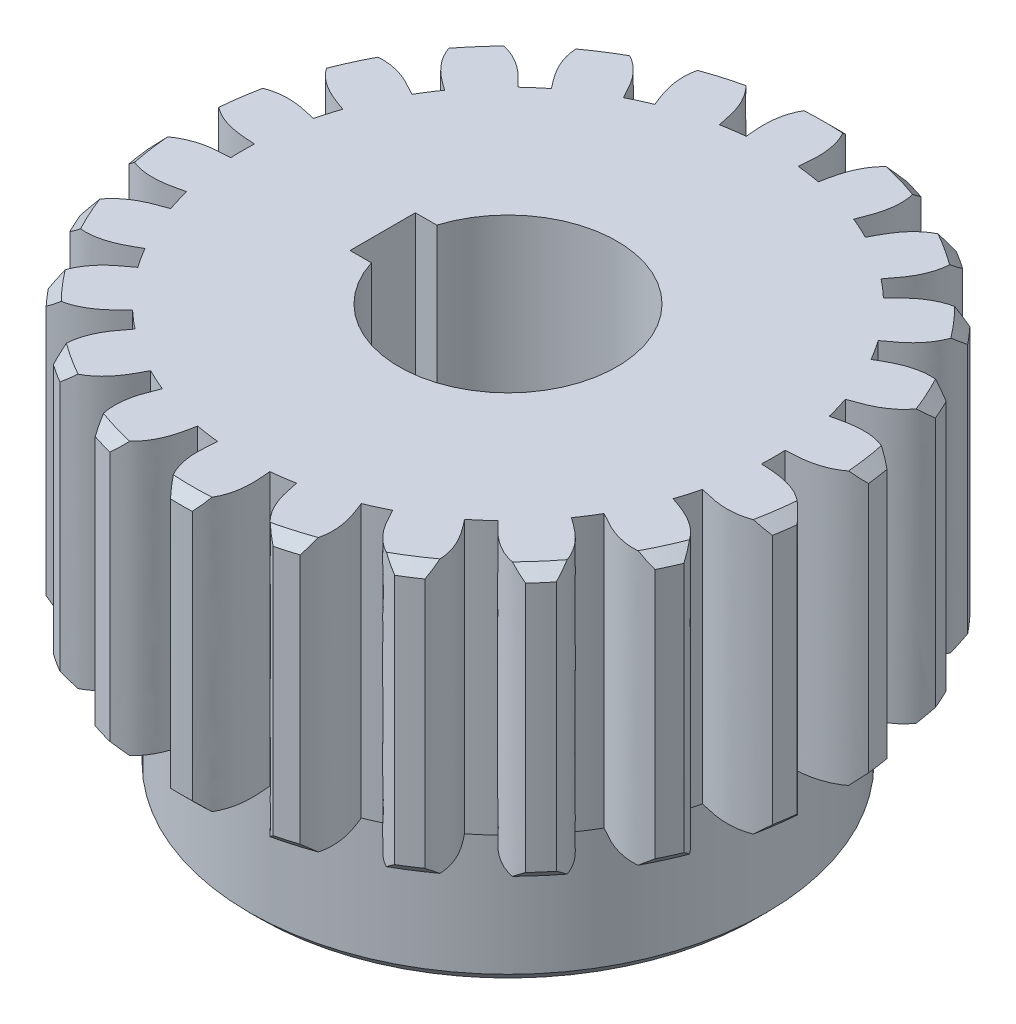
SolidWorks part; units mm, degrees
ref_plane "前基準面" through (0, 0, 0) normal (0, 0, 1) x (1, 0, 0)
ref_plane "上基準面" through (0, 0, 0) normal (0, 1, 0) x (1, 0, 0)
ref_plane "右基準面" through (0, 0, 0) normal (1, 0, 0) x (0, 0, -1)
sketch "草圖1" plane through (0, 0, 0) normal (0, 0, 1) x (1, 0, 0)
  line L0 (0, -10.9151) -> (0, 15.1539) construction
  line L1 (20, 50) -> (60, 50)
  line L2 (60, 50) -> (60, 0)
  line L3 (60, 0) -> (47.5, 0)
  line L4 (47.5, 0) -> (47.5, -25)
  line L5 (47.5, -25) -> (20, -25)
  line L6 (20, -25) -> (20, 50)
  dimension "D1" = 75
  dimension "D2" = 50
  dimension "D3" = 40
  dimension "D4" = 120
  dimension "D5" = 95
revolve "旋轉1" add sketch "草圖1" angle 360 about L0
sketch "草圖2" plane through (0, 50, 0) normal (0, 1, 0) x (1, 0, 0)
  line L0 (0, 0) -> (-25.7975, 0) construction
  line L1 (-23, 6) -> (-11, 6)
  line L2 (-23, 6) -> (-23, -6)
  line L3 (-23, -6) -> (-11, -6)
  line L4 (-11, 6) -> (-11, -6)
  circle A0 centre (0, 0) radius 20 construction
  dimension "D1" = 43
  dimension "D2" = 12
extrude "除料-伸長1" cut sketch "草圖2" against normal up to next
chamfer "導角1" distance 2 angle 45 3 edges at (0, 0, -60) (0, 50, -60) (0, -25, -47.5)
sketch "草圖7" plane through (0, 0, 0) normal (0, -1, 0) x (1, 0, 0)
  line L0 (0, 0) -> (-66.5332, 0) construction
  circle A0 centre (0, 0) radius 55 construction
  arc A1 (-48.7016, 2.1717) -> (-48.7016, -2.1717) centre (0, 0) ccw
  circle A2 centre (0, 0) radius 60 construction
  arc A3 (-59.641, 6.5536) -> (-59.641, -6.5536) centre (0, 0) ccw
  circle A4 centre (0, 0) radius 58 construction
  circle A5 centre (0, 0) radius 60 construction
  spline S0 degree 3 poles (-59.641, 6.5536) (-59.0593, 5.9065) (-57.2741, 3.9209) (-53.2816, 2.3848) (-50.0991, 2.2367) (-48.7016, 2.1717) knots 0 0 0 0 0.213285 0.654527 1 1 1 1
  spline S1 degree 3 poles (-59.641, -6.5536) (-59.0593, -5.9065) (-57.2741, -3.9209) (-53.2816, -2.3848) (-50.0991, -2.2367) (-48.7016, -2.1717) knots 0 0 0 0 0.213285 0.654527 1 1 1 1
  dimension "D1" = 110
  dimension "D2" = 48.75
extrude "除料-伸長2" cut sketch "草圖7" against normal up to next
pattern_circular "環狀複製排列1" count 22 every 16.364 about axis through (0, 50.001, 0) along (0, -1, 0) of "除料-伸長2"
ref_plane "平面1" through (-60, 0, 0) normal (1, 0, 0) x (0, 0, -1)
hole_wizard "M8 螺紋孔1" positions "草圖4" profile "草圖3" tap size "M8" standard "GB" end condition up to next
sketch "草圖4" plane through (-60, 10, 0) normal (1, 0, 0) x (0, 0, -1)
  line L0 (0, -20.9151) -> (0, 5.1539) construction
  line L1 (-47.5, -35) -> (47.5, -35) construction
  point P0 (0, -25)
  dimension "D1" = 10
cosmetic thread "鑽孔螺紋1" parameters "D2"=8
sketch "草圖3" plane through (-60, -15, 0) normal (0, 1, 0) x (0, 0, 1)
  line L0 (0, 0) -> (0, 37)
  line L1 (0, 37) -> (3.4, 37)
  line L2 (3.4, 37) -> (3.4, 0)
  line L5 (3.4, 0) -> (0, 0)
  line L11 (0, -6.35) -> (0, 107.95) construction
  dimension "貫穿螺孔鑽直徑" = 6.8
  dimension "貫穿螺孔鑽深度" = 37
ref_plane "平面2" through (0, 0, -60) normal (0, 0, 1) x (1, 0, 0)
hole_wizard "M8 螺紋孔2" positions "草圖6" profile "草圖5" tap size "M8" standard "GB" end condition up to next
sketch "草圖6" plane through (0, 0, -60) normal (0, 0, 1) x (1, 0, 0)
  line L0 (0, -10.9151) -> (0, 15.1539) construction
  line L1 (-47.5, -25) -> (47.5, -25) construction
  point P0 (0, -15)
  dimension "D1" = 10
sketch "草圖5" plane through (0, -15, -60) normal (1, 0, 0) x (0, 1, 0)
  line L0 (0, 0) -> (0, 40)
  line L1 (0, 40) -> (3.4, 40)
  line L2 (3.4, 40) -> (3.4, 0)
  line L5 (3.4, 0) -> (0, 0)
  line L11 (0, -6.35) -> (0, 107.95) construction
  dimension "貫穿螺孔鑽直徑" = 6.8
  dimension "貫穿螺孔鑽深度" = 40
cosmetic thread "鑽孔螺紋2" parameters "D2"=8
